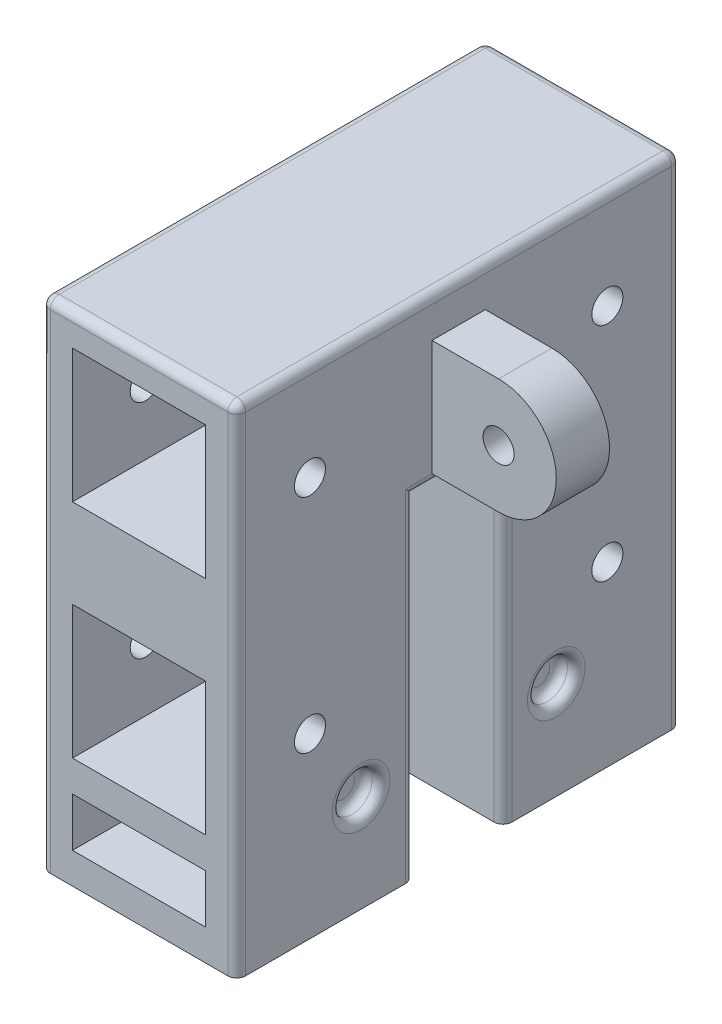
SolidWorks part; units mm, degrees
ref_plane "Front Plane" through (0, 0, 0) normal (0, 0, 1) x (1, 0, 0)
ref_plane "Top Plane" through (0, 0, 0) normal (0, 1, 0) x (1, 0, 0)
ref_plane "Right Plane" through (0, 0, 0) normal (1, 0, 0) x (0, 0, -1)
sketch "Sketch1" plane through (0, 0, 0) normal (0, 0, 1) x (1, 0, 0)
  line L1 (-25.0962, 42.3339) -> (-3.0962, 42.3339)
  line L2 (-25.0962, 42.3339) -> (-25.0962, -13.6661)
  line L3 (-25.0962, -13.6661) -> (-3.0962, -13.6661)
  line L4 (-3.0962, 42.3339) -> (-3.0962, -13.6661)
  line L5 (-21.5962, 38.8339) -> (-6.5962, 38.8339)
  line L6 (-21.5962, 38.8339) -> (-21.5962, 23.8339)
  line L7 (-21.5962, 23.8339) -> (-6.5962, 23.8339)
  line L8 (-6.5962, 38.8339) -> (-6.5962, 23.8339)
  dimension "D1" = 22
  dimension "D2" = 56
  dimension "D3" = 15
  dimension "D4" = 3.5
  dimension "D5" = 3.5
  dimension "D6" = 15
extrude "Boss-Extrude1" add sketch "Sketch1" along normal blind 20
sketch "Sketch2" plane through (0, 0, 20) normal (0, 0, 1) x (1, 0, 0)
  line L0 (-3.0962, -13.6661) -> (-3.0962, 42.3339) construction
  line L1 (-21.5962, 13.8339) -> (-6.5962, 13.8339)
  line L2 (-21.5962, 13.8339) -> (-21.5962, -1.1661)
  line L3 (-21.5962, -1.1661) -> (-6.5962, -1.1661)
  line L4 (-6.5962, 13.8339) -> (-6.5962, -1.1661)
  line L5 (-21.5962, 23.8339) -> (-6.5962, 23.8339) construction
  line L6 (-25.0962, -13.6661) -> (-3.0962, -13.6661) construction
  line L7 (-21.5962, -4.6661) -> (-6.5962, -4.6661)
  line L8 (-21.5962, -4.6661) -> (-21.5962, -10.1661)
  line L9 (-21.5962, -10.1661) -> (-6.5962, -10.1661)
  line L10 (-6.5962, -4.6661) -> (-6.5962, -10.1661)
  dimension "D1" = 15
  dimension "D2" = 3.5
  dimension "D3" = 10
  dimension "D4" = 15
  dimension "D5" = 15
  dimension "D6" = 3.5
  dimension "D7" = 3.5
extrude "Cut-Extrude1" cut sketch "Sketch2" against normal offset from surface (15.5 mm away) 4.5 up to face at (-14.0962, 14.3339, 0)
sketch "Sketch3" plane through (-25.0962, 0, 0) normal (-1, 0, 0) x (0, 0, 1)
  line L0 (11.75, -13.6661) -> (11.75, 43.4795) construction
  line L1 (20, -13.6661) -> (0, -13.6661) construction
  line L3 (20, 38.8339) -> (0, 38.8339) construction
  line L4 (4.5, 13.8339) -> (20, 13.8339) construction
  line L5 (20, 42.3339) -> (20, -13.6661) construction
  circle A0 centre (11.75, 31.3339) radius 1.75
  circle A1 centre (11.75, 6.3339) radius 1.75
  dimension "D2" = 3.5
  dimension "D3" = 7.5
  dimension "D4" = 7.5
  dimension "D1" = 8.25
extrude "Cut-Extrude2" cut sketch "Sketch3" against normal blind 35
ref_plane "Plane1" through (0, 0, -5) normal (0, 0, -1) x (-1, 0, 0)
mirror "Mirror3" about plane through (0, 0, -5) normal (0, 0, -1) of bodies 104
sketch "Sketch4" plane through (0, 0, 0) normal (0, 0, -1) x (-1, 0, 0)
  line L0 (6.5962, 38.8339) -> (21.5962, 38.8339) construction
  line L1 (6.5962, 23.8339) -> (6.5962, 38.8339) construction
  line L3 (21.5962, 38.8339) -> (21.5962, 23.8339) construction
  line L4 (6.5962, 38.8339) -> (21.5962, 38.8339)
  line L5 (6.5962, 23.8339) -> (6.5962, 38.8339)
  line L7 (21.5962, 38.8339) -> (21.5962, 23.8339)
  line L8 (3.0962, 42.3339) -> (25.0962, 42.3339) construction
  line L9 (3.0962, 42.3339) -> (25.0962, 42.3339)
  line L10 (3.0962, 42.3339) -> (3.0962, 23.8339)
  line L11 (3.0962, -13.6661) -> (3.0962, 42.3339) construction
  line L12 (3.0962, 23.8339) -> (6.5962, 23.8339)
  line L13 (25.0962, 42.3339) -> (25.0962, -13.6661) construction
  line L14 (25.0962, 23.8339) -> (25.0962, 42.3339)
  line L15 (21.5962, 23.8339) -> (25.0962, 23.8339)
extrude "Boss-Extrude2" add sketch "Sketch4" along normal up to surface (10 mm away) up to face at (-14.0962, 14.3339, -10)
sketch "Sketch6" plane through (0, 0, -5) normal (0, 0, -1) x (-1, 0, 0)
  line L0 (6.5962, 31.3339) -> (-4.4038, 31.3339) construction
  line L1 (6.5962, 23.8339) -> (6.5962, 38.8339) construction
  line L2 (-4.4038, 37.8339) -> (3.0962, 37.8339)
  line L3 (3.0962, -13.6661) -> (3.0962, 42.3339) construction
  line L4 (3.0962, 37.8339) -> (3.0962, 24.8339)
  line L5 (3.0962, 24.8339) -> (-4.4038, 24.8339)
  circle A0 centre (-4.4038, 31.3339) radius 1.75
  arc A1 (-4.4038, 37.8339) -> (-4.4038, 24.8339) centre (-4.4038, 31.3339) ccw
  dimension "D1" = 3.5
  dimension "D2" = 13
  dimension "D3" = 11
extrude "Boss-Extrude3" add sketch "Sketch6" along normal blind 3 and the other way blind 3
sketch "Sketch7" plane through (-3.0962, 0, 0) normal (1, 0, 0) x (0, 0, -1)
  line L0 (-20, -2.6661) -> (30, -2.6661) construction
  line L1 (-20, -13.6661) -> (-20, 42.3339) construction
  line L2 (30, -13.6661) -> (30, 42.3339) construction
  line L3 (30, -13.6661) -> (10, -13.6661) construction
  line L4 (10, -13.6661) -> (10, 23.8339) construction
  line L5 (0, -13.6661) -> (0, 23.8339) construction
  circle A0 centre (16, -2.6661) radius 2.25
  circle A1 centre (-6, -2.6661) radius 2.25
  dimension "D2" = 6
  dimension "D3" = 6
  dimension "D4" = 4.5
  dimension "D1" = 11
extrude "Cut-Extrude3" cut sketch "Sketch7" against normal blind 2
fillet "Fillet1" radius 1 4 edges at (-5.0962, -0.4161, -16) (-5.0962, -0.4161, 6) (-3.0962, -0.4161, 6) (-3.0962, -0.4161, -16)
fillet "Fillet2" radius 1 14 edges at (-25.0962, 42.3339, -5) (-14.0962, 42.3339, -30) (-14.0962, 42.3339, 20) (-3.0962, 14.3339, -30) (-25.0962, 14.3339, -30) (-25.0962, 14.3339, 20) (-3.0962, 14.3339, 20) (-3.0962, 42.3339, -5)
